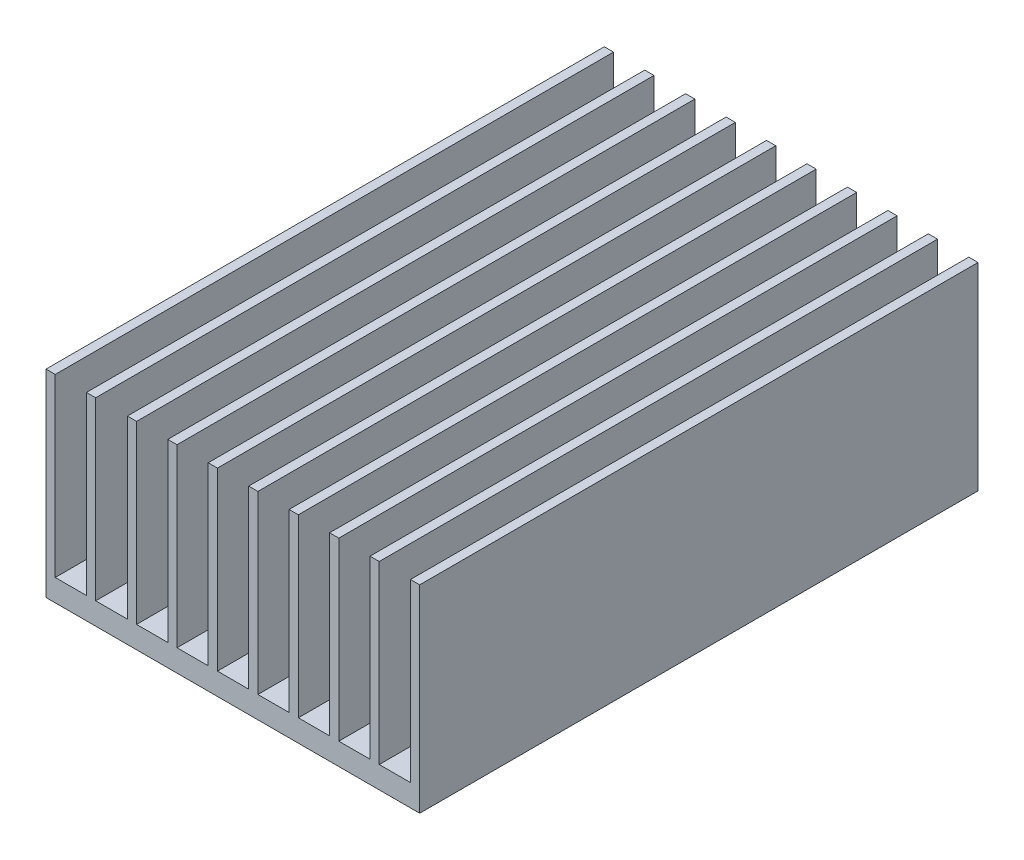
SolidWorks part; units mm, degrees
material "1060 Alloy"
ref_plane "Ön Düzlem" through (0, 0, 0) normal (0, 0, 1) x (1, 0, 0)
ref_plane "Üst Düzlem" through (0, 0, 0) normal (0, 1, 0) x (1, 0, 0)
ref_plane "Sağ Düzlem" through (0, 0, 0) normal (1, 0, 0) x (0, 0, -1)
ref_plane "Plane1" through (0, 0, -127) normal (0, 0, -1) x (-1, 0, 0)
sketch "Sketch1" plane through (0, 0, -127) normal (0, 0, -1) x (-1, 0, 0)
  line L0 (85, 45) -> (82.9, 45)
  line L1 (82.9, 45) -> (82.9, 5)
  line L2 (82.9, 5) -> (75.8, 5)
  line L3 (75.8, 5) -> (75.8, 45)
  line L4 (75.8, 45) -> (73.7, 45)
  line L5 (73.7, 45) -> (73.7, 5)
  line L6 (73.7, 5) -> (66.5, 5)
  line L7 (66.5, 5) -> (66.5, 45)
  line L8 (66.5, 45) -> (64.4, 45)
  line L9 (64.4, 45) -> (64.4, 5)
  line L10 (64.4, 5) -> (57.3, 5)
  line L11 (57.3, 5) -> (57.3, 45)
  line L12 (57.3, 45) -> (55.2, 45)
  line L13 (55.2, 45) -> (55.2, 5)
  line L14 (55.2, 5) -> (48.1, 5)
  line L15 (48.1, 5) -> (48.1, 45)
  line L16 (48.1, 45) -> (46, 45)
  line L17 (46, 45) -> (46, 5)
  line L18 (46, 5) -> (38.9, 5)
  line L19 (38.9, 5) -> (38.9, 45)
  line L20 (38.9, 45) -> (36.8, 45)
  line L21 (36.8, 45) -> (36.8, 5)
  line L22 (36.8, 5) -> (29.7, 5)
  line L23 (29.7, 5) -> (29.7, 45)
  line L24 (29.7, 45) -> (27.6, 45)
  line L25 (27.6, 45) -> (27.6, 5)
  line L26 (27.6, 5) -> (20.5, 5)
  line L27 (20.5, 5) -> (20.5, 45)
  line L28 (20.5, 45) -> (18.4, 45)
  line L29 (18.4, 45) -> (18.4, 5)
  line L30 (18.4, 5) -> (11.3, 5)
  line L31 (11.3, 5) -> (11.3, 45)
  line L32 (11.3, 45) -> (9.2, 45)
  line L33 (9.2, 45) -> (9.2, 5)
  line L34 (9.2, 5) -> (2.1, 5)
  line L35 (2.1, 5) -> (2.1, 45)
  line L36 (2.1, 45) -> (0, 45)
  line L37 (0, 45) -> (0, 0)
  line L38 (0, 0) -> (85, 0)
  line L39 (85, 0) -> (85, 45)
extrude "Boss-Extrude1" add sketch "Sketch1" against normal blind 127
sketch "Sketch4" plane through (0, 0, 0) normal (0, -1, 0) x (-1, 0, 0)
  line L1 (46.6614, 78.9178) -> (33.2902, 78.9178)
  line L2 (46.6614, 78.9178) -> (46.6614, 54.9042)
  line L3 (46.6614, 54.9042) -> (33.2902, 54.9042)
  line L4 (33.2902, 78.9178) -> (33.2902, 54.9042)
extrude "thermal-paste" add sketch "Sketch4" along normal blind 2 contours L3 L4 L1 L2
split "Split1" bodies to split 107 resulting bodies 108 109 split by face at (-42.5, 0, -63.5)
